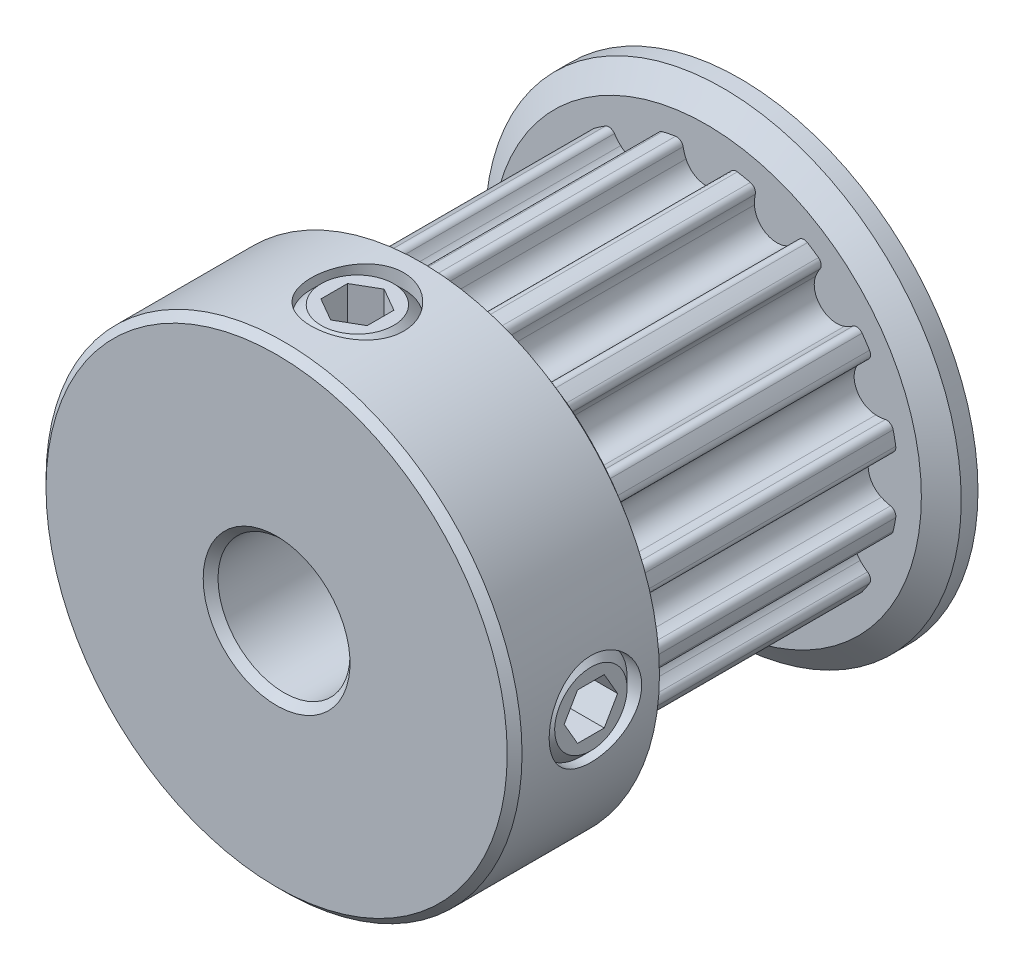
SolidWorks part; units mm, degrees
ref_plane "Front Plane" through (0, 0, 0) normal (0, 0, 1) x (1, 0, 0)
ref_plane "Top Plane" through (0, 0, 0) normal (0, 1, 0) x (1, 0, 0)
ref_plane "Right Plane" through (0, 0, 0) normal (1, 0, 0) x (0, 0, -1)
sketch "Sketch1" plane through (0, 0, 0) normal (0, 0, 1) x (1, 0, 0)
  line L1 (-2.553, 6.1245) -> (2.553, 6.1245) construction
  line L4 (0, 0) -> (0, 6.1245) construction
  line L5 (0, 6.1245) -> (0, 12.0714) construction
  line L6 (0, 7.6455) -> (2.9417, 7.0569) construction
  line L7 (2.9417, 7.0569) -> (3.8741, 6.6682) construction
  line L8 (2.9417, 7.0569) -> (2.553, 6.1245) construction
  line L9 (-2.9417, 7.0569) -> (-2.553, 6.1245) construction
  line L10 (-2.7951, 6.7052) -> (-3.7579, 9.015)
  line L11 (-3.7579, 9.015) -> (3.7579, 9.015)
  line L12 (3.7579, 9.015) -> (2.7951, 6.7052)
  circle A0 centre (0, 0) radius 7.6455 construction
  circle A1 centre (0, 0) radius 9.015 construction
  circle A2 centre (0, 0) radius 7.2645 construction
  arc A3 (-0.7739, 6.6229) -> (0.7739, 6.6229) centre (0, 6.9745) ccw
  arc A4 (-0.7739, 6.6229) -> (-0.8836, 6.9694) centre (0.61, 7.2516) cw
  arc A5 (-2.7951, 6.7052) -> (-1.1695, 7.1697) centre (0, 0) cw
  arc A6 (-0.8836, 6.9694) -> (-1.1695, 7.1697) centre (-1.1292, 6.923) ccw
  arc A7 (2.7951, 6.7052) -> (1.1695, 7.1697) centre (0, 0) ccw
  arc A8 (0.8836, 6.9694) -> (1.1695, 7.1697) centre (1.1292, 6.923) cw
  arc A9 (0.7739, 6.6229) -> (0.8836, 6.9694) centre (-0.61, 7.2516) ccw
  point P6 (0, 20.9083)
  point P11 (0, 7.6455)
  point P13 (0, 9.015)
  point P14 (0, 7.2645)
  dimension "D1" = 8.8369
  dimension "D2" = 4.4259
sketch "Sketch2" plane through (0, 0, 0) normal (1, 0, 0) x (0, 0, -1)
  line L0 (-8.775, 2.5) -> (8.775, 2.5)
  line L1 (-8.775, 2.5) -> (-8.775, 9.015)
  line L2 (-3.29, 9.015) -> (-8.775, 9.015)
  line L3 (-3.925, 2.5) -> (-3.925, 9.015) construction
  line L4 (-3.925, 9.015) -> (-2.655, 9.015) construction
  line L5 (-2.655, 9.015) -> (-2.655, 7.2645) construction
  line L6 (-2.655, 7.2645) -> (7.505, 7.2645)
  line L7 (7.505, 7.2645) -> (7.505, 9.015) construction
  line L8 (7.505, 9.015) -> (8.775, 9.015) construction
  line L9 (8.775, 9.015) -> (8.775, 2.5)
  line L10 (-8.775, 0) -> (8.775, 0) construction
  line L11 (8.14, 9.015) -> (7.505, 8.1398)
  line L12 (-2.655, 8.1398) -> (-3.29, 9.015)
  line L14 (-2.655, 8.1398) -> (-2.655, 7.2645)
  line L15 (7.505, 7.2645) -> (7.505, 8.1398)
  line L16 (8.14, 9.015) -> (8.775, 9.015)
  arc A0 (-2.655, 8.1398) -> (-3.29, 9.015) centre (-3.5757, 8.1398) ccw construction
  arc A1 (7.505, 8.1398) -> (8.14, 9.015) centre (8.4257, 8.1398) cw construction
  point P12 (-2.655, 8.1398)
  point P14 (-3.29, 9.015)
  point P20 (7.505, 8.1398)
  point P21 (8.14, 9.015)
  point P25 (7.505, 0)
  point P26 (-2.655, 0)
  dimension "OA" = 17.55
  dimension "Bore" = 5
  dimension "Outside Width" = 11.43
  dimension "Inside Width" = 10.16
revolve "Revolve1" add sketch "Sketch2" angle 360 mid plane about L10
sketch "Sketch3" plane through (0, 0, 0) normal (0, 0, 1) x (1, 0, 0)
  line L6 (3.7579, 9.015) -> (-3.7579, 9.015)
  line L7 (2.7951, 6.7052) -> (3.7579, 9.015)
  line L8 (-3.7579, 9.015) -> (-2.7951, 6.7052)
  line L9 (3.7579, 9.015) -> (-3.7579, 9.015)
  line L10 (2.7951, 6.7052) -> (3.7579, 9.015)
  line L11 (-3.7579, 9.015) -> (-2.7951, 6.7052)
  arc A8 (2.7951, 6.7052) -> (1.1695, 7.1697) centre (0, 0) ccw
  arc A9 (1.1695, 7.1697) -> (0.8836, 6.9694) centre (1.1292, 6.923) ccw
  arc A10 (0.7739, 6.6229) -> (0.8836, 6.9694) centre (-0.61, 7.2516) ccw
  arc A11 (-0.7739, 6.6229) -> (0.7739, 6.6229) centre (0, 6.9745) ccw
  arc A12 (-0.8836, 6.9694) -> (-0.7739, 6.6229) centre (0.61, 7.2516) ccw
  arc A13 (-0.8836, 6.9694) -> (-1.1695, 7.1697) centre (-1.1292, 6.923) ccw
  arc A14 (-1.1695, 7.1697) -> (-2.7951, 6.7052) centre (0, 0) ccw
  arc A15 (2.7951, 6.7052) -> (1.1695, 7.1697) centre (0, 0) ccw
  arc A16 (1.1695, 7.1697) -> (0.8836, 6.9694) centre (1.1292, 6.923) ccw
  arc A17 (0.7739, 6.6229) -> (0.8836, 6.9694) centre (-0.61, 7.2516) ccw
  arc A18 (-0.7739, 6.6229) -> (0.7739, 6.6229) centre (0, 6.9745) ccw
  arc A19 (-0.8836, 6.9694) -> (-0.7739, 6.6229) centre (0.61, 7.2516) ccw
  arc A20 (-0.8836, 6.9694) -> (-1.1695, 7.1697) centre (-1.1292, 6.923) ccw
  arc A21 (-1.1695, 7.1697) -> (-2.7951, 6.7052) centre (0, 0) ccw
  dimension "D1" = 0
extrude "Cut-Extrude1" cut sketch "Sketch3" against normal up to vertex (7.505 mm away) from vertex up to point (0, 7.2645, -7.505) starting at point (0, 7.2645, 2.655)
pattern_circular "CirPattern1" count 16 over 360 about axis through (0, 0, 8.775) along (0, 0, 1) of "Cut-Extrude1"
sketch "Sketch4" plane through (0, 0, 0) normal (1, 0, 0) x (0, -1, 0)
  line L0 (0, -2.655) -> (0, -8.775) construction
  line L1 (-2.5, -8.775) -> (2.5, -8.775) construction
  line L2 (8.1398, -2.655) -> (-8.1398, -2.655) construction
  circle A0 centre (0, -5.715) radius 1.7526
extrude "Cut-Extrude2" cut sketch "Sketch4" along normal through all
ref_plane "Plane1" through (0, 0, 5.715) normal (0, 0, 1) x (1, 0, 0)
sketch "Sketch5" plane through (0, 0, 5.715) normal (0, 0, 1) x (1, 0, 0)
  line L0 (0, 0) -> (0, 9.015) construction
  line L1 (2.5, -1.3716) -> (2.5, 0)
  line L2 (2.881, -1.7526) -> (8.462, -1.7526)
  line L3 (2.5, 0) -> (9.015, 0) construction
  line L4 (2.5, 0) -> (8.843, 0)
  line L5 (8.843, 0) -> (8.843, -1.3716)
  line L6 (2.881, -1.7526) -> (2.5, -1.3716)
  line L7 (8.843, -1.3716) -> (8.462, -1.7526)
  circle A0 centre (0, 0) radius 9.015 construction
  circle A1 centre (0, 0) radius 2.5 construction
  point P2 (2.5, -1.7526)
  point P11 (8.843, -1.7526)
revolve "Revolve2" add sketch "Sketch5" angle 360 mid plane about L4
sketch "Sketch6" plane through (8.843, 5.3841, 0) normal (-1, 0, 0) x (0, -1, 0)
  line L1 (5.3841, 6.7269) -> (4.5078, 6.2209)
  line L2 (4.5078, 6.2209) -> (4.5078, 5.2091)
  line L3 (4.5078, 5.2091) -> (5.3841, 4.7031)
  line L4 (5.3841, 4.7031) -> (6.2604, 5.2091)
  line L5 (6.2604, 5.2091) -> (6.2604, 6.2209)
  line L6 (6.2604, 6.2209) -> (5.3841, 6.7269)
  circle A0 centre (5.3841, 5.715) radius 0.8763 construction
  dimension "D1" = 1.7526
extrude "Cut-Extrude3" cut sketch "Sketch6" along normal blind 1.3144
pattern_circular "CirPattern3" count 2 over 90 about axis through (0, 0, 8.775) along (0, 0, 1) of "Cut-Extrude2", "Revolve2", "Cut-Extrude3"
chamfer "Chamfer1" distance 0.2807 angle 45 2 edges at (2.5, 0, 8.775) (9.015, 0, 8.775)
ref_axis "Center Axis 1" through (0, 0, -8.775) along (0, 0, 1)
ref_plane "Contact Plane 1" through (0, 0, 8.775) normal (0, 0, 1) x (1, 0, 0)
ref_plane "Contact Plane 2" through (0, 0, -8.775) normal (0, 0, -1) x (-1, 0, 0)
equation "\"D2@Sketch1\"= \"D1@Sketch1\" / 2"
equation "\"D1@Sketch6\" = \"Set Screw@Sketch4\" / 2"
equation "\"D1@Cut-Extrude3\" = \"D1@Sketch6\"*.75"
